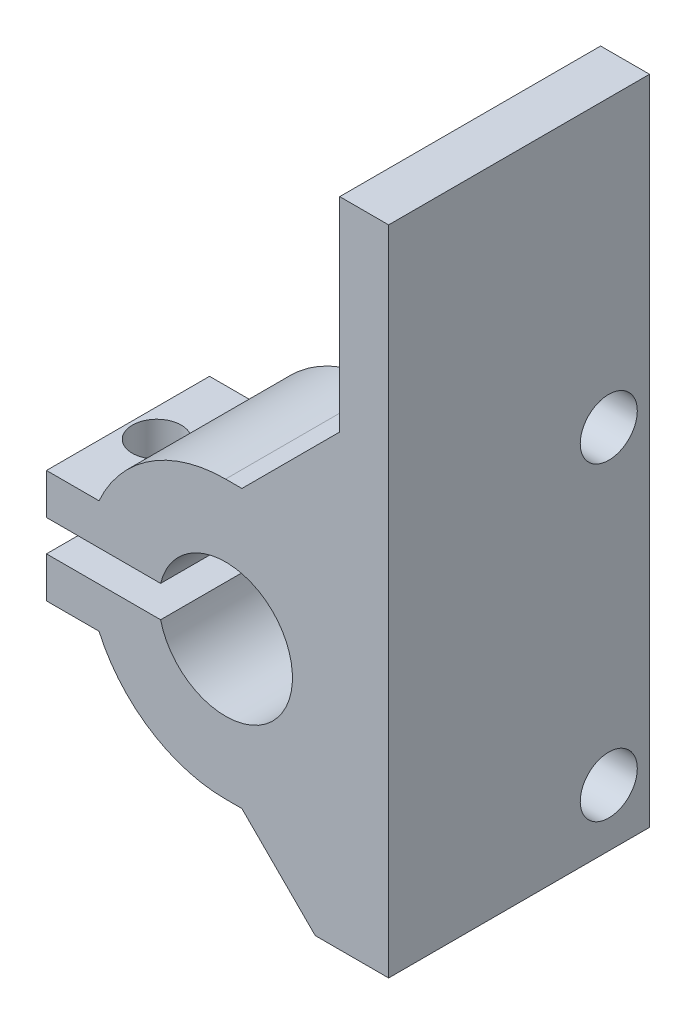
SolidWorks part; units mm, degrees
ref_plane "Plano frontal" through (0, 0, 0) normal (0, 0, 1) x (1, 0, 0)
ref_plane "Plano superior" through (0, 0, 0) normal (0, 1, 0) x (1, 0, 0)
ref_plane "Plano direito" through (0, 0, 0) normal (1, 0, 0) x (0, 0, -1)
sketch "Esboço1" plane through (0, 0, 0) normal (0, 0, 1) x (1, 0, 0)
  line L5 (0, 8.5) -> (8.5, 8.5)
  line L6 (8.5, 8.5) -> (8.5, 0)
  line L7 (-3.9849, 0.9647) -> (-10.9849, 0.9647)
  line L8 (-10.9849, 0.9647) -> (-10.9849, 3.4647)
  line L9 (-10.9849, 3.4647) -> (-7.7618, 3.4647)
  line L13 (-7.7618, -3.4647) -> (-10.9849, -3.4647)
  line L14 (-10.9849, -0.9647) -> (-10.9849, -3.4647)
  line L15 (-10.9849, -0.9647) -> (-3.9849, -0.9647)
  line L17 (0, -8.5) -> (8.5, -8.5)
  line L18 (8.5, -8.5) -> (8.5, 0)
  arc A0 (-3.9849, -0.9647) -> (-3.9849, 0.9647) centre (0, 0) ccw
  arc A1 (-7.7618, -3.4647) -> (0, -8.5) centre (0, 0) ccw
  arc A2 (0, 8.5) -> (-7.7618, 3.4647) centre (0, 0) ccw
  dimension "D1" = 8.2
  dimension "D2" = 17
  dimension "D3" = 7
  dimension "D4" = 7
  dimension "D5" = 2.5
extrude "Ressalto-extrusão1" add sketch "Esboço1" along normal blind 10
sketch "Esboço2" plane through (0, 3.4647, 0) normal (0, 1, 0) x (1, 0, 0)
  line L1 (-7.7618, -10) -> (-7.7618, 0) construction
  circle A0 centre (-9.2618, -4.9556) radius 3.25
  dimension "D1" = 6.5
  dimension "D2" = 1.5
extrude "Corte-extrusão1" cut sketch "Esboço2" along normal blind 10
ref_plane "Plano1" through (6, 0, 0) normal (1, 0, 0) x (0, 0, -1)
sketch "Esboço3" plane through (0, 3.4647, 0) normal (0, 1, 0) x (1, 0, 0)
  circle A0 centre (-9.2618, -4.9556) radius 1.5
  arc A1 (-7.7618, -7.8387) -> (-7.7618, -2.0724) centre (-9.2618, -4.9556) ccw construction
  dimension "D1" = 3
extrude "Corte-extrusão2" cut sketch "Esboço3" against normal blind 10
sketch "Esboço4" plane through (0, -3.4647, 0) normal (0, -1, 0) x (-1, 0, 0)
  circle A0 centre (9.2618, -4.9556) radius 3.25
  circle A1 centre (9.2618, -4.9556) radius 1.5 construction
  dimension "D1" = 6.5
extrude "Corte-extrusão3" cut sketch "Esboço4" along normal blind 10
sketch "Esboço5" plane through (6, 0, 0) normal (1, 0, 0) x (0, 0, -1)
  line L1 (-10, 27) -> (6, 27)
  line L2 (-10, 27) -> (-10, -13)
  line L3 (-10, -13) -> (6, -13)
  line L4 (6, 27) -> (6, -13)
  line L5 (-10, 27) -> (6, -13) construction
  line L6 (-10, -13) -> (6, 27) construction
  line L7 (-10, -8.5) -> (-10, 8.5) construction
  line L8 (3.5, -9.5) -> (3.5, 9.5) construction
  circle A0 centre (3.5, 9.5) radius 1.75
  circle A1 centre (3.5, -9.5) radius 1.75
  point P4 (-2, 7)
  point P12 (3.5, 0)
  dimension "D5" = 3.5
  dimension "D1" = 16
  dimension "D2" = 40
  dimension "D3" = 19
  dimension "D4" = 3.5
  dimension "D6" = 2.5
extrude "Ressalto-extrusão2" add sketch "Esboço5" along normal blind 4
chamfer "Chanfro1" distance 5 angle 45 1 edges at (6, 8.5, 5)
chamfer "Chanfro2" distance 5 angle 45 1 edges at (6, -8.5, 5)
chamfer "Chanfro3" distance 1 angle 45 4 edges at (6, 20.25, 10) (6, -13, -3) (6, 7, -6) (6, 27, 2)
